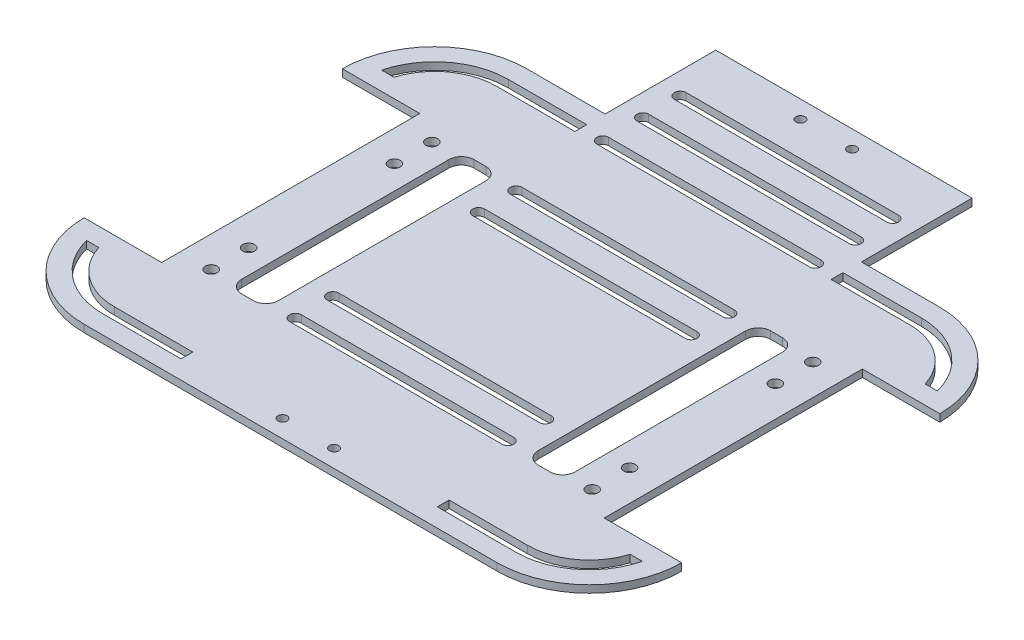
SolidWorks part; units mm, degrees
ref_plane "Front Plane" through (0, 0, 0) normal (0, 0, 1) x (1, 0, 0)
ref_plane "Top Plane" through (0, 0, 0) normal (0, 1, 0) x (1, 0, 0)
ref_plane "Right Plane" through (0, 0, 0) normal (1, 0, 0) x (0, 0, -1)
sketch "Sketch1" plane through (0, 0, 0) normal (0, 1, 0) x (1, 0, 0)
  line L0 (0, 0) -> (0, -79.375)
  line L1 (7.1438, -66.675) -> (-7.1437, -66.675)
  line L2 (50.8, 22.225) -> (76.2, 22.225)
  line L3 (-63.5, -47.625) -> (-50.8, -47.625)
  line L4 (-50.8, -47.625) -> (-50.8, 22.225)
  line L5 (63.5, -47.625) -> (50.8, -47.625)
  line L6 (50.8, -47.625) -> (50.8, 22.225)
  line L7 (-50.8, 22.225) -> (-76.2, 22.225)
  line L8 (0, 0) -> (-27.2811, 0)
  circle A0 centre (0, 0) radius 79.375
  circle A1 centre (-7.1437, -66.675) radius 1.5875
  circle A2 centre (7.1438, -66.675) radius 1.5875
  circle A3 centre (7.1438, 66.675) radius 1.5875
  circle A4 centre (-7.1437, 66.675) radius 1.5875
  point P7 (0, -66.675)
  dimension "D1" = 7.1437
  dimension "D3" = 50.8
  dimension "D6" = 3.175
  dimension "D2" = 12.7
  dimension "D4" = 69.85
  dimension "D5" = 47.625
extrude "Boss-Extrude5" add sketch "Sketch1" along normal blind 1.5875 contours A2 A0 L5 L6 L2 L7 L4 L3 A1 A3 region at (0, 0, -2.0947)
fillet "Fillet2" radius 2.54 1 edges at (-63.5, 0.7937, 47.625)
fillet "Fillet3" radius 2.54 1 edges at (63.5, 0.7937, 47.625)
fillet "Fillet4" radius 5.08 2 edges at (-76.2, 0.7937, -22.225) (76.2, 0.7937, -22.225)
sketch "Sketch2" plane through (0, 1.5875, 0) normal (0, 1, 0) x (1, 0, 0)
  line L0 (0, 0) -> (0, 79.375)
  line L1 (0, 0) -> (-67.0566, 0)
  line L2 (0, 0) -> (-61.0886, 27.6545)
  line L3 (0, 0) -> (-43.6778, 50.8806)
  line L4 (0, 0) -> (-63.2664, 22.225)
  line L5 (-50.8, 22.225) -> (-69.0955, 22.225) construction
  line L6 (0, 0) -> (0, 2.6153)
  line L7 (0, 0) -> (-39.0771, 54.4938)
  line L8 (0, 0) -> (-12.3858, 65.9028)
  line L9 (-62.5348, 28.3092) -> (-59.6424, 26.9998)
  line L10 (-43.6778, 50.8806) -> (-44.7118, 52.0852)
  line L11 (-43.6778, 50.8806) -> (-42.6438, 49.6761)
  line L12 (-39.0771, 54.4938) -> (-40.0022, 55.7839)
  line L13 (-39.0771, 54.4938) -> (-38.152, 53.2037)
  line L14 (-43.6778, 50.8806) -> (-42.6438, 49.6761)
  line L15 (-12.3858, 65.9028) -> (-12.0926, 64.3426)
  line L16 (-12.3858, 65.9028) -> (-12.679, 67.463)
  line L17 (61.5813, 22.225) -> (64.9466, 22.225)
  line L18 (50.8, 22.225) -> (69.0955, 22.225) construction
  line L19 (12.3858, 65.9028) -> (12.679, 67.463)
  line L20 (12.3858, 65.9028) -> (12.0926, 64.3426)
  line L21 (39.0771, 54.4938) -> (38.152, 53.2037)
  line L22 (43.6778, 50.8806) -> (42.6438, 49.6761)
  line L23 (39.0771, 54.4938) -> (40.0022, 55.7839)
  line L24 (43.6778, 50.8806) -> (42.6438, 49.6761)
  line L25 (43.6778, 50.8806) -> (44.7118, 52.0852)
  line L26 (62.5348, 28.3092) -> (59.6424, 26.9998)
  line L27 (-50.8, -41.2985) -> (-50.8, -43.7716)
  line L28 (-50.8, -47.625) -> (-50.8, 22.225) construction
  line L29 (50.8, -41.2985) -> (50.8, -46.1668)
  line L30 (50.8, -47.625) -> (50.8, 22.225) construction
  line L31 (39.0771, -54.4938) -> (40.0022, -55.7839)
  line L32 (39.0771, -54.4938) -> (38.152, -53.2037)
  line L33 (12.3858, -65.9028) -> (12.0926, -64.3426)
  line L34 (12.3858, -65.9028) -> (12.679, -67.463)
  line L35 (-12.3858, -65.9028) -> (-12.679, -67.463)
  line L36 (-12.3858, -65.9028) -> (-12.0926, -64.3426)
  line L37 (-39.0771, -54.4938) -> (-38.152, -53.2037)
  line L38 (-39.0771, -54.4938) -> (-40.0022, -55.7839)
  arc A0 (-63.2664, 22.225) -> (-50.8, -43.7716) centre (0, 0) ccw
  arc A1 (73.8199, 29.172) -> (-73.8199, 29.172) centre (0, 0) ccw construction
  circle A2 centre (-7.1437, 66.675) radius 2.3813
  circle A3 centre (7.1437, 66.675) radius 2.3813
  circle A4 centre (7.1437, -66.675) radius 2.3813
  circle A5 centre (-7.1437, -66.675) radius 2.3813
  arc A6 (12.679, -67.463) -> (40.0022, -55.7839) centre (0, 0) ccw
  arc A7 (-61.7686, 21.6988) -> (-50.8, -41.2985) centre (0, 0) ccw
  arc A8 (-44.7118, 52.0852) -> (-62.5348, 28.3092) centre (0, 0) ccw
  arc A9 (-42.6438, 49.6761) -> (-59.6424, 26.9998) centre (0, 0) ccw
  arc A10 (12.0926, 64.3426) -> (38.152, 53.2037) centre (0, 0) cw
  arc A11 (12.679, 67.463) -> (40.0022, 55.7839) centre (0, 0) cw
  arc A12 (42.6438, 49.6761) -> (59.6424, 26.9998) centre (0, 0) cw
  arc A13 (-12.679, 67.463) -> (-40.0022, 55.7839) centre (0, 0) ccw
  arc A14 (44.7118, 52.0852) -> (62.5348, 28.3092) centre (0, 0) cw
  arc A15 (-12.0926, 64.3426) -> (-38.152, 53.2037) centre (0, 0) ccw
  arc A16 (12.0926, -64.3426) -> (38.152, -53.2037) centre (0, 0) ccw
  arc A17 (-12.0926, -64.3426) -> (-38.152, -53.2037) centre (0, 0) cw
  arc A18 (50.8, -46.1668) -> (64.9466, 22.225) centre (0, 0) ccw
  arc A19 (50.8, -43.7716) -> (63.2664, 22.225) centre (0, 0) ccw
  arc A20 (50.8, -41.2985) -> (61.5813, 22.225) centre (0, 0) ccw
  arc A21 (-12.679, -67.463) -> (-40.0022, -55.7839) centre (0, 0) cw
  circle M13 centre (-7.1437, -66.675) radius 1.5875
  circle M14 centre (7.1438, -66.675) radius 1.5875
  circle M15 centre (7.1438, 66.675) radius 1.5875
  circle M16 centre (-7.1437, 66.675) radius 1.5875
  dimension "D2" = 4.7625
  dimension "D7" = 1.5875
  dimension "D8" = 3.175
  dimension "D1" = 5
  dimension "D3" = 25
  dimension "D4" = 5
  dimension "D5" = 25
extrude "Cut-Extrude1" cut sketch "Sketch2" against normal blind 2.54 contours A9 L3 L10 A8 L9 L2 | A15 L8 L16 A13 L12 L7 | A2 M16 | A3 M15 | A11 L19 L20 A10 L21 L23 | A14 L25 L22 A12 L26 | A21 L35 L36 A17 L37 L38 | A5 M13 | A4 M14 | A16 L33 L34 A6 L31 L32 region at (-53.2404, 1.5875, -39.9101) region at (-26.1525, 1.5875, -61.1833) region at (26.1525, 1.5875, -61.1833) region at (53.2404, 1.5875, -39.9101) region at (26.1525, 1.5875, 61.1833) region at (-26.1525, 1.5875, 61.1833) region at (-9.4576, 1.5875, -66.675) region at (4.8299, 1.5875, -66.675) region at (4.8299, 1.5875, 66.675) region at (-9.4576, 1.5875, 66.675)
sketch "Sketch3" plane through (0, 1.5875, 0) normal (0, 1, 0) x (1, 0, 0)
  line L0 (-50.8, 22.225) -> (-50.8, -47.625)
  line L1 (-50.8, -47.625) -> (-44.45, -47.625)
  line L2 (-50.8, 22.225) -> (-44.45, 22.225)
  line L3 (0, 0) -> (0, 32.9013)
  circle A0 centre (-44.45, -47.625) radius 1.5875
  circle A1 centre (-44.45, 22.225) radius 1.5875
  circle A2 centre (44.45, 22.225) radius 1.5875
  circle A3 centre (44.45, -47.625) radius 1.5875
  dimension "D2" = 3.175
  dimension "D4" = 3.175
  dimension "D1" = 6.35
  dimension "D3" = 6.35
extrude "Cut-Extrude2" cut sketch "Sketch3" against normal blind 2.54 contours A1 | A2 | A0 | A3 region at (-44.45, 1.5875, 46.0824) region at (-44.45, 1.5875, -23.7676) region at (44.45, 1.5875, -22.225) region at (44.45, 1.5875, 47.625)
sketch "Sketch4" plane through (0, 1.5875, 0) normal (0, 1, 0) x (1, 0, 0)
  line L0 (-44.45, -47.625) -> (-44.45, 22.225)
  line L1 (-44.45, 22.225) -> (-50.8, 22.225)
  line L2 (-50.8, -47.625) -> (-50.8, 22.225) construction
  line L3 (0, 0) -> (0, -67.5878)
  line L4 (44.45, -47.625) -> (44.45, 22.225)
  circle A0 centre (-44.45, 22.225) radius 1.5875
  circle A1 centre (-44.45, -12.7) radius 1.5875
  circle A2 centre (44.45, -12.7) radius 1.5875
  dimension "D2" = 3.175
  dimension "D1" = 69.85
extrude "Cut-Extrude3" cut sketch "Sketch4" against normal blind 2.54 contours L0 A1 | L0 A1 | A2 L4 | A2 L4 region at (-45.1238, 1.5875, 12.7) region at (-43.7762, 1.5875, 12.7) region at (43.7762, 1.5875, 12.7) region at (45.1238, 1.5875, 12.7)
sketch "Sketch5" plane through (0, 1.5875, 0) normal (0, 1, 0) x (1, 0, 0)
  line L0 (-50.8, -12.7) -> (-34.8, -12.7)
  line L1 (-50.8, -47.625) -> (-50.8, 22.225) construction
  line L2 (-50.8, 22.225) -> (-34.8, 22.225)
  line L3 (-34.8, 22.225) -> (-34.8, -12.7)
  line L4 (0, 0) -> (0, 64.5379)
  line L5 (-34.8, 22.225) -> (-19.8, 22.225)
  line L6 (-19.8, 22.225) -> (-19.8, -12.7)
  line L7 (-19.8, -12.7) -> (-34.8, -12.7)
  line L8 (19.8, -12.7) -> (34.8, -12.7)
  line L9 (19.8, 22.225) -> (19.8, -12.7)
  line L10 (34.8, 22.225) -> (19.8, 22.225)
  line L11 (34.8, 22.225) -> (34.8, -12.7)
  dimension "D1" = 16
  dimension "D2" = 16
extrude "Cut-Extrude4" cut sketch "Sketch5" against normal through all contours L7 L6 L5 L3 | L11 L10 L9 L8 region at (-27.3, 1.5875, -4.7625) region at (27.3, 1.5875, -4.7625)
fillet "Fillet5" radius 7.62 4 edges at (-19.8, 0.7937, 12.7) (-34.8, 0.7937, 12.7) (-19.8, 0.7937, -22.225) (-34.8, 0.7937, -22.225)
fillet "Fillet6" radius 7.62 4 edges at (34.8, 0.7937, 12.7) (34.8, 0.7937, -22.225) (19.8, 0.7937, -22.225) (19.8, 0.7937, 12.7)
sketch "Sketch6" plane through (0, 0, 0) normal (0, -1, 0) x (-1, 0, 0)
  circle A0 centre (0, 0) radius 79.375
extrude "Cut-Extrude5" cut sketch "Sketch6" against normal blind 0.5875
sketch "Sketch8" plane through (0, 1.5875, 0) normal (0, 1, 0) x (1, 0, 0)
  line L0 (-50.8, 22.225) -> (-50.8, 24.225)
  line L1 (-50.8, 24.225) -> (-80.2365, 24.225)
  line L2 (0, 0) -> (0, 19.3161)
  line L3 (0, 0) -> (-9.6505, 0)
  line L4 (50.8, 24.225) -> (80.2365, 24.225)
  line L5 (50.8, 22.225) -> (50.8, 24.225)
  line L6 (-50.8, -47.625) -> (-50.8, -49.625)
  line L7 (-50.8, -49.625) -> (-75.4506, -49.625)
  line L8 (50.8, -49.625) -> (75.4506, -49.625)
  line L9 (50.8, -47.625) -> (50.8, -49.625)
  line L10 (-50.8, -47.625) -> (-75.4506, -47.625)
  line L11 (-75.4506, -47.625) -> (-75.4506, -49.625)
  line L12 (50.8, -47.625) -> (75.4506, -47.625)
  line L13 (75.4506, -49.625) -> (75.4506, -47.625)
  line L14 (50.8, 22.225) -> (80.2365, 22.225)
  line L15 (80.2365, 22.225) -> (80.2365, 24.225)
  line L16 (-50.8, 22.225) -> (-80.2365, 22.225)
  line L17 (-80.2365, 22.225) -> (-80.2365, 24.225)
extrude "Cut-Extrude6" cut sketch "Sketch8" against normal blind 2.54 contours L10 L11 L7 L6 | L8 L13 L12 L9 | L14 L15 L4 L5 | L1 L17 L16 L0 region at (65.5183, 1.5875, -23.225) region at (-63.1253, 1.5875, 48.625) region at (63.1253, 1.5875, 48.625)
fillet "Fillet7" radius 2.54 4 edges at (-60.6806, 1.0875, 49.625) (60.6806, 1.0875, 49.625) (73.1353, 1.0875, -24.225) (-73.1353, 1.0875, -24.225)
sketch "Sketch11" plane through (0, 1.5875, 0) normal (0, 1, 0) x (1, 0, 0)
  line L1 (-11.0583, 60.7829) -> (11.2037, 60.7829)
  line L2 (-11.0583, 60.7829) -> (-11.0583, 72.1091)
  line L3 (-11.0583, 72.1091) -> (11.2037, 72.1091)
  line L4 (11.2037, 60.7829) -> (11.2037, 72.1091)
  line L5 (-11.0583, -61.658) -> (11.2037, -61.658)
  line L6 (-11.0583, -61.658) -> (-11.0583, -72.2032)
  line L7 (-11.0583, -72.2032) -> (11.2037, -72.2032)
  line L8 (11.2037, -61.658) -> (11.2037, -72.2032)
extrude "Boss-Extrude7" add sketch "Sketch11" against normal up to surface (1 mm away) up to face at (0, 0.5875, 5.2491)
sketch "Sketch12" plane through (0, 1.5875, 0) normal (0, 1, 0) x (1, 0, 0)
  line L0 (0, 0) -> (0, 79.375)
  line L1 (0, 0) -> (-6.75, 0)
  line L4 (0, 65.9028) -> (-6.75, 65.9028)
  line L5 (0, -65.9028) -> (-6.75, -65.9028)
  line L6 (-12.3858, -65.9028) -> (12.3858, -65.9028)
  line L7 (-12.0926, -64.3426) -> (-12.679, -67.463) construction
  line L8 (12.679, -67.463) -> (12.0926, -64.3426) construction
  arc A0 (73.8199, 29.172) -> (-73.8199, 29.172) centre (0, 0) ccw construction
  circle A1 centre (-6.75, 65.9028) radius 1.25
  circle A2 centre (6.75, 65.9028) radius 1.25
  circle A3 centre (6.75, -65.9028) radius 1.25
  circle A4 centre (-6.75, -65.9028) radius 1.25
  dimension "D1" = 2.5
  dimension "D2" = 13.5
extrude "Cut-Extrude7" cut sketch "Sketch12" against normal blind 2.54 contours A4 L6 | A4 L6 | L6 A3 | L6 A3 | A1 | A2 region at (-6.75, 1.5875, 66.4333) region at (-6.75, 1.5875, 65.3723) region at (6.75, 1.5875, 65.3723) region at (6.75, 1.5875, 66.4333) region at (-7.9646, 1.5875, -65.9028) region at (6.75, 1.5875, -65.9028)
sketch "Sketch14" plane through (0, 1.5875, 0) normal (0, 1, 0) x (1, 0, 0)
  circle A0 centre (-44.45, -12.7) radius 1.5875
  circle A2 centre (44.45, -12.7) radius 1.5875
  dimension "D1" = 3.175
extrude "Boss-Extrude8" add sketch "Sketch14" against normal up to surface (1 mm away) up to face at (-6.75, 0.5875, 64.6528)
sketch "Sketch15" plane through (0, 1.5875, 0) normal (0, 1, 0) x (1, 0, 0)
  line L0 (-44.45, 22.225) -> (-44.45, -1.0583)
  line L1 (-44.45, -1.0583) -> (-44.45, -24.3417)
  line L2 (0, 0) -> (0, 10.0728)
  line L3 (44.45, -1.0583) -> (44.45, -24.3417)
  circle A0 centre (-44.45, -1.0583) radius 1.5875
  circle A1 centre (-44.45, -24.3417) radius 1.5875
  circle A2 centre (44.45, -24.3417) radius 1.5875
  circle A3 centre (44.45, -1.0583) radius 1.5875
  dimension "D1" = 23.2833
  dimension "D2" = 3.175
  dimension "D3" = 23.2833
extrude "Cut-Extrude8" cut sketch "Sketch15" against normal blind 2.54 contours L1 A0 L0 | L0 A0 L1 | A1 | A2 | A3 region at (-43.7762, 1.5875, 1.0583) region at (-43.3592, 1.5875, 23.2509) region at (-45.1238, 1.5875, 1.0583) region at (45.5408, 1.5875, 23.2509) region at (43.3592, 1.5875, -0.0324)
sketch "Sketch16" plane through (0, 1.5875, 0) normal (0, 1, 0) x (1, 0, 0)
  line L0 (-44.45, -1.0583) -> (-51.5937, -1.0583)
  line L1 (-50.8, -49.625) -> (-56.413, -49.625) construction
  line L2 (-50.8, 24.225) -> (-51.5937, 24.225)
  line L3 (-50.8, 24.225) -> (-50.8, -49.625)
  line L4 (-50.8, -49.625) -> (-51.5937, -49.625)
  line L5 (-51.5937, 24.225) -> (-51.5937, -49.625)
  line L6 (0, 0) -> (0, 12.3631)
  line L7 (51.5937, 24.225) -> (51.5937, -49.625)
  line L8 (50.8, -49.625) -> (51.5937, -49.625)
  line L9 (50.8, 24.225) -> (50.8, -49.625)
  line L10 (50.8, 24.225) -> (51.5937, 24.225)
extrude "Boss-Extrude13" add sketch "Sketch16" against normal up to surface (1 mm away) contours L2 L5 L0 L3 | L0 L5 L4 L3 | L10 L9 L8 L7 region at (-51.1969, 1.5875, 25.3417) region at (-51.1969, 1.5875, -11.5833) region at (51.1969, 1.5875, 12.7) up to face at (44.45, 0.5875, 22.7542)
sketch "Sketch17" plane through (0, 1.5875, 0) normal (0, 1, 0) x (1, 0, 0)
  line L0 (0, 0) -> (0, 79.375)
  line L1 (0, 0) -> (-11.9199, 67.6013)
  line L2 (0, 0) -> (12.0176, 0)
  line L3 (0, 0) -> (-62.5348, 28.3092)
  line L4 (0, 0) -> (11.9199, 67.6013)
  line L5 (0, 0) -> (62.5348, 28.3092)
  line L6 (0, 0) -> (-40.0022, -55.7839)
  line L7 (0, 0) -> (11.9199, -67.6013)
  line L8 (0, 0) -> (-11.9199, -67.6013)
  line L9 (0, 0) -> (40.0022, -55.7839)
  arc A0 (73.8199, 29.172) -> (-73.8199, 29.172) centre (0, 0) ccw construction
  circle A1 centre (0, 0) radius 68.6441
  circle A2 centre (0, 0) radius 65.4691
  dimension "D1" = 10
extrude "Cut-Extrude10" cut sketch "Sketch17" against normal through all contours A2 L1 A1 L3 | A2 L5 A1 L4 | A2 L7 A1 L9 | A2 L6 A1 L8 region at (-40.5469, 1.5875, -52.2313) region at (12.2875, 1.5875, -65.9244) region at (-25.7975, 1.5875, 61.3039) region at (25.7975, 1.5875, 61.3039)
sketch "Sketch18" plane through (0, 1.5875, 0) normal (0, 1, 0) x (1, 0, 0)
  line L0 (0, 0) -> (0, 79.375)
  line L1 (0, 0) -> (-26.9517, 0)
  line L2 (0, 0) -> (-11.9199, 67.6013)
  line L3 (0, 0) -> (-34.3221, 59.4475)
  line L4 (0, 0) -> (-44.1236, 52.5844)
  line L5 (0, 0) -> (-59.4475, 34.3221)
  line L6 (-62.5348, 28.3092) -> (-59.6424, 26.9998)
  line L7 (0, 0) -> (11.9199, 67.6013)
  line L8 (0, 0) -> (34.3221, 59.4475)
  line L9 (0, 0) -> (44.1236, 52.5844)
  line L10 (0, 0) -> (59.4475, 34.3221)
  line L11 (0, 0) -> (44.1236, -52.5844)
  line L12 (0, 0) -> (-44.1236, -52.5844)
  line L13 (0, 0) -> (34.3221, -59.4475)
  line L14 (0, 0) -> (11.9199, -67.6013)
  line L15 (0, 0) -> (-11.9199, -67.6013)
  line L16 (0, 0) -> (-34.3221, -59.4475)
  line L17 (59.6424, 26.9998) -> (62.5348, 28.3092)
  line L18 (40.0022, -55.7839) -> (38.152, -53.2037)
  line L19 (-38.152, -53.2037) -> (-40.0022, -55.7839)
  arc A0 (73.8199, 29.172) -> (-73.8199, 29.172) centre (0, 0) ccw construction
  circle A1 centre (0, 0) radius 68.6441
  circle A2 centre (0, 0) radius 65.4691
  dimension "D1" = 20
  dimension "D2" = 10
  dimension "D3" = 20
extrude "Boss-Extrude16" add sketch "Sketch18" against normal up to surface (1 mm away) contours A2 L19 A1 L16 | A2 L13 A1 L18 | A2 L17 A1 L10 | A2 L9 A1 L8 | A2 L3 A1 L4 | A2 L5 A1 L6 region at (-38.4205, 1.5875, -54.8701) region at (-59.64, 1.5875, -30.6219) region at (38.4205, 1.5875, -54.8701) region at (59.64, 1.5875, -30.6219) region at (36.3389, 1.5875, 56.3393) region at (-36.3389, 1.5875, 56.3393) up to face at (25.6849, 0.5875, 61.0364)
sketch "Sketch19" plane through (0, 1.5875, 0) normal (0, 1, 0) x (1, 0, 0)
  line L0 (33.7, 150.1124) -> (33.7, 185.1124)
  line L1 (0, 79.375) -> (0, -79.375)
  line L2 (-51.5937, 24.225) -> (51.5937, 24.225)
  line L3 (-51.5937, 24.225) -> (-51.5937, -49.625)
  line L4 (-51.5937, -49.625) -> (51.5937, -49.625)
  line L5 (51.5937, 24.225) -> (51.5937, -49.625)
  line L6 (37.7, 90.1124) -> (149.7, 90.1124)
  line L7 (-172.4279, 149.4503) -> (-117.4279, 149.4503)
  line L8 (-172.4279, 149.4503) -> (-172.4279, 121.4503)
  line L9 (-172.4279, 121.4503) -> (-117.4279, 121.4503)
  line L10 (-117.4279, 149.4503) -> (-117.4279, 121.4503)
  line L11 (219.5866, 324.1917) -> (264.5866, 324.1917)
  line L12 (219.5866, 324.1917) -> (219.5866, 272.1917)
  line L13 (219.5866, 272.1917) -> (264.5866, 272.1917)
  line L14 (264.5866, 324.1917) -> (264.5866, 272.1917)
  line L15 (51.5937, -49.625) -> (11.5937, -49.625)
  line L16 (51.5937, -49.625) -> (51.5937, -14.625)
  line L17 (51.5937, -14.625) -> (11.5937, -14.625)
  line L18 (11.5937, -49.625) -> (11.5937, -14.625)
  line L19 (93.7, 90.1124) -> (93.7, 230.1124)
  line L21 (174.7, 115.1124) -> (153.7, 115.1124)
  line L22 (12.7, 185.1124) -> (33.7, 185.1124)
  line L23 (78.6997, 149.9601) -> (87.6997, 149.9296)
  line L24 (38.7, 167.1124) -> (38.7, 133.1124)
  line L25 (78.6427, 133.1124) -> (38.7, 133.1124)
  line L26 (78.7578, 167.1124) -> (78.6427, 133.1124)
  line L27 (78.7578, 167.1124) -> (38.7, 167.1124)
  line L28 (33.7, 150.1124) -> (12.7, 150.1124)
  line L29 (242.0866, 324.1917) -> (242.0866, 272.1917)
  line L30 (37.7, 210.1124) -> (58.953, 210.1124)
  line L31 (290.0855, 218.8978) -> (400.0855, 218.8978)
  line L32 (290.0855, 218.8978) -> (290.0855, 165.8978)
  line L33 (290.0855, 165.8978) -> (400.0855, 165.8978)
  line L34 (400.0855, 218.8978) -> (400.0855, 165.8978)
  line L35 (-58.953, -52.165) -> (-58.953, 24.225)
  line L36 (-51.5937, 24.225) -> (-71.5774, 24.225) construction
  line L37 (-58.953, 24.225) -> (-51.5937, 24.225)
  line L38 (-58.953, -52.165) -> (-51.5937, -49.625)
  line L39 (58.953, -52.165) -> (51.5937, -49.625)
  line L40 (58.953, 24.225) -> (51.5937, 24.225)
  line L41 (58.953, -52.165) -> (58.953, 24.225)
  line L42 (51.5937, 24.225) -> (51.5937, -49.625)
  line L43 (12.7, 120.1124) -> (12.7, 180.1124)
  line L44 (12.7, 180.1124) -> (22.7, 180.1124)
  line L45 (22.7, 180.1124) -> (22.7, 120.1124)
  line L46 (22.7, 120.1124) -> (12.7, 120.1124)
  line L47 (38.7, 150.1124) -> (33.7, 150.1124)
  line L49 (128.447, 230.1124) -> (128.447, 210.1124)
  line L50 (153.7, 150.1124) -> (153.7, 115.1124)
  line L51 (148.7, 150.1124) -> (153.7, 150.1124)
  line L52 (164.7, 120.1124) -> (174.7, 120.1124)
  line L53 (164.7, 180.1124) -> (164.7, 120.1124)
  line L54 (174.7, 180.1124) -> (164.7, 180.1124)
  line L55 (174.7, 120.1124) -> (174.7, 180.1124)
  line L56 (149.7, 210.1124) -> (128.447, 210.1124)
  line L57 (33.7, 150.1124) -> (33.7, 115.1124)
  line L58 (153.7, 150.1124) -> (174.7, 150.1124)
  line L59 (108.6422, 167.1124) -> (148.7, 167.1124)
  line L60 (108.6422, 167.1124) -> (108.7573, 133.1124)
  line L61 (108.7573, 133.1124) -> (148.7, 133.1124)
  line L62 (58.953, 230.1124) -> (58.953, 210.1124)
  line L63 (174.7, 185.1124) -> (153.7, 185.1124)
  line L64 (148.7, 167.1124) -> (148.7, 133.1124)
  line L65 (108.7003, 149.9601) -> (99.7003, 149.9296)
  line L66 (153.7, 150.1124) -> (153.7, 185.1124)
  line L67 (-325.826, 349.5435) -> (-272.826, 349.5435)
  line L68 (-325.826, 349.5435) -> (-325.826, 239.5435)
  line L69 (-325.826, 239.5435) -> (-272.826, 239.5435)
  line L70 (-272.826, 349.5435) -> (-272.826, 239.5435)
  line L71 (-215.9733, 300.1641) -> (-187.9733, 300.1641)
  line L72 (-215.9733, 300.1641) -> (-215.9733, 245.1641)
  line L73 (-215.9733, 245.1641) -> (-187.9733, 245.1641)
  line L74 (-187.9733, 300.1641) -> (-187.9733, 245.1641)
  line L75 (12.7, 115.1124) -> (33.7, 115.1124)
  line L76 (153.7, 180.1124) -> (153.7, 150.1124)
  line L78 (58.953, 230.1124) -> (58.953, 240.1124)
  line L79 (58.953, 240.1124) -> (128.447, 240.1124)
  line L80 (128.447, 230.1124) -> (128.447, 240.1124)
  arc A0 (73.8199, 29.172) -> (-73.8199, 29.172) centre (0, 0) ccw construction
  arc A1 (-58.2779, -53.8895) -> (58.2779, -53.8895) centre (0, 0) ccw construction
  arc A2 (-56.413, -49.625) -> (-58.2779, -53.8895) centre (-56.413, -52.165) ccw construction
  circle A3 centre (100.706, 94.8953) radius 1.25
  circle A4 centre (86.694, 235.3295) radius 1.25
  circle A5 centre (86.694, 94.8953) radius 1.25
  circle A6 centre (100.706, 235.3295) radius 1.25
  arc A7 (12.7, 115.1124) -> (37.7, 90.1124) centre (37.7, 115.1124) ccw
  arc A8 (174.7, 115.1124) -> (149.7, 90.1124) centre (149.7, 115.1124) cw
  arc A9 (12.7, 185.1124) -> (37.7, 210.1124) centre (37.7, 185.1124) cw
  arc A10 (174.7, 185.1124) -> (149.7, 210.1124) centre (149.7, 185.1124) ccw
  dimension "D15" = 55
  dimension "D1" = 103.1875
  dimension "D3" = 158.75
  dimension "D4" = 28
  dimension "D5" = 55
  dimension "D6" = 150
  dimension "D7" = 162
  dimension "D8" = 40
  dimension "D9" = 35
  dimension "D11" = 110
  dimension "D12" = 110
  dimension "D13" = 53
  dimension "D16" = 28
  dimension "D17" = 53
  dimension "D18" = 45
  dimension "D19" = 52
  dimension "D20" = 29.75
extrude "Boss-Extrude20" add sketch "Sketch19" along normal blind 2 separate body contours L63 A10 L56 L49 L80 L79 L78 L62 L30 A9 L22 L0 L24 L27 L26 L25 L57 L75 A7 L6 A8 L21 L50 L64 L61 L60 L59 L66 A4 A3 A5 | L26 L27 L24 L25 | L64 L59 L60 L61 region at (58.7001, 1.5875, -150.1206) region at (128.6999, 1.5875, -150.1206) region at (35.9078, 1.5875, -167.6124)
sketch "Sketch20" plane through (0, 3.5875, 0) normal (0, 1, 0) x (1, 0, 0)
  line L0 (33.7, 185.1124) -> (33.7, 180.0324)
  line L1 (33.7, 115.1124) -> (33.7, 185.1124) construction
  line L2 (42.05, 180.0324) -> (33.7, 180.0324)
  line L3 (33.7, 180.0324) -> (33.7, 175.0324)
  line L4 (33.7, 150.1124) -> (44.1466, 150.1124)
  line L5 (93.7, 240.1124) -> (93.7, 224.3413)
  line L6 (58.953, 240.1124) -> (128.447, 240.1124) construction
  circle A0 centre (42.05, 180.0324) radius 1.5875
  circle A1 centre (42.05, 169.8724) radius 1.5875
  circle A2 centre (42.05, 130.3524) radius 1.5875
  circle A3 centre (42.05, 120.1924) radius 1.5875
  circle A4 centre (145.35, 120.1924) radius 1.5875
  circle A5 centre (145.35, 130.3524) radius 1.5875
  circle A6 centre (145.35, 169.8724) radius 1.5875
  circle A7 centre (145.35, 180.0324) radius 1.5875
  dimension "D3" = 3.175
  dimension "D5" = 3.175
  dimension "D1" = 5.08
  dimension "D2" = 5
  dimension "D4" = 10.16
  dimension "D6" = 8.35
extrude "Cut-Extrude13" cut sketch "Sketch20" against normal blind 2 contours A0 | A1 | A2 | A3 | A4 | A5 | A6 | A7 region at (42.05, 3.5875, -178.4898) region at (42.05, 3.5875, -169.8724) region at (42.05, 3.5875, -130.3524) region at (42.05, 3.5875, -120.1924) region at (145.35, 3.5875, -120.1924) region at (145.35, 3.5875, -130.3524) region at (145.35, 3.5875, -169.8724) region at (145.35, 3.5875, -180.0324)
sketch "Sketch23" plane through (0, 3.5875, 0) normal (0, 1, 0) x (1, 0, 0)
  line L0 (64.903, 181.6324) -> (122.497, 181.6324)
  line L1 (122.497, 178.4324) -> (64.903, 178.4324)
  line L2 (37.7, 205.1124) -> (58.953, 205.1124)
  line L3 (122.497, 226.1324) -> (64.903, 226.1324)
  line L4 (37.7, 201.9124) -> (58.953, 201.9124)
  line L5 (122.497, 222.9324) -> (64.903, 222.9324)
  line L6 (122.497, 171.4724) -> (64.903, 171.4724)
  line L7 (64.903, 168.2724) -> (122.497, 168.2724)
  line L8 (169.0649, 190.1124) -> (165.7387, 190.1124)
  line L9 (93.7, 230.3124) -> (93.7, 236.6657)
  line L10 (58.953, 205.1124) -> (58.953, 201.9124)
  line L11 (-100.9547, 278.8038) -> (-40.9547, 278.8038)
  line L12 (-100.9547, 278.8038) -> (-100.9547, 248.8038)
  line L13 (-100.9547, 248.8038) -> (-40.9547, 248.8038)
  line L14 (-40.9547, 278.8038) -> (-40.9547, 248.8038)
  line L15 (122.497, 215.9724) -> (64.903, 215.9724)
  line L16 (-24.4507, 290.9638) -> (-63.4507, 290.9638)
  line L17 (-24.4507, 287.7638) -> (-63.4507, 287.7638)
  line L18 (-63.4507, 246.4638) -> (-24.4507, 246.4638)
  line L19 (-63.4507, 244.8638) -> (-24.4507, 244.8638)
  line L20 (-65.0507, 289.3638) -> (-65.0507, 244.8638)
  line L21 (-24.4507, 243.2638) -> (-63.4507, 243.2638)
  line L22 (-22.8507, 244.8638) -> (-22.8507, 289.3638)
  line L23 (122.497, 212.7724) -> (64.903, 212.7724)
  line L24 (18.3351, 190.1124) -> (21.6613, 190.1124)
  line L25 (12.7, 185.1124) -> (33.7, 185.1124) construction
  line L26 (64.903, 131.9524) -> (122.497, 131.9524)
  line L27 (122.497, 128.7524) -> (64.903, 128.7524)
  line L28 (122.497, 121.7924) -> (64.903, 121.7924)
  line L29 (64.903, 118.5924) -> (122.497, 118.5924)
  line L30 (128.447, 205.1124) -> (128.447, 201.9124)
  line L33 (64.903, 205.1124) -> (122.497, 205.1124)
  line L34 (64.903, 201.9124) -> (122.497, 201.9124)
  line L35 (128.447, 205.1124) -> (149.7, 205.1124)
  line L36 (128.447, 201.9124) -> (149.7, 201.9124)
  line L37 (33.7, 150.1124) -> (40.3143, 150.1124)
  line L38 (33.7, 115.1124) -> (33.7, 185.1124) construction
  line L39 (18.3351, 110.1124) -> (21.6613, 110.1124)
  line L40 (58.953, 95.1124) -> (58.953, 98.3124)
  line L41 (37.7, 98.3124) -> (58.953, 98.3124)
  line L42 (37.7, 95.1124) -> (58.953, 95.1124)
  line L43 (149.7, 95.1124) -> (128.447, 95.1124)
  line L44 (149.7, 98.3124) -> (128.447, 98.3124)
  line L45 (128.447, 95.1124) -> (128.447, 98.3124)
  line L46 (169.0649, 110.1124) -> (165.7387, 110.1124)
  line L47 (51.8765, 181.6324) -> (55.0765, 181.6324)
  line L48 (-34.8, 14.605) -> (-19.8, 14.605)
  line L49 (-34.8, 14.605) -> (-34.8, -5.08)
  line L50 (-34.8, -5.08) -> (-19.8, -5.08)
  line L51 (-19.8, 14.605) -> (-19.8, -5.08)
  line L52 (58.4765, 178.2324) -> (58.4765, 121.9924)
  line L53 (53.4765, 181.6324) -> (53.4765, 210.1124)
  line L54 (58.4765, 121.9924) -> (58.8603, 122.0299)
  line L55 (37.7, 210.1124) -> (58.953, 210.1124) construction
  line L56 (58.953, 210.1124) -> (58.953, 240.1124) construction
  line L57 (55.0765, 118.5924) -> (51.8765, 118.5924)
  line L58 (51.8765, 118.5924) -> (51.3797, 118.9575)
  line L59 (48.4765, 121.9924) -> (48.4765, 178.2324)
  line L60 (138.9235, 121.9924) -> (138.9235, 178.2324)
  line L61 (135.5235, 118.5924) -> (136.0203, 118.9575)
  line L62 (132.3235, 118.5924) -> (135.5235, 118.5924)
  line L63 (128.9235, 121.9924) -> (128.5397, 122.0299)
  line L64 (128.9235, 178.2324) -> (128.9235, 121.9924)
  line L65 (135.5235, 181.6324) -> (132.3235, 181.6324)
  arc A0 (-63.4507, 290.9638) -> (-63.4507, 287.7638) centre (-63.4507, 289.3638) ccw
  arc A1 (64.903, 226.1324) -> (64.903, 222.9324) centre (64.903, 224.5324) ccw
  arc A2 (122.497, 226.1324) -> (122.497, 222.9324) centre (122.497, 224.5324) cw
  arc A3 (64.903, 181.6324) -> (64.903, 178.4324) centre (64.903, 180.0324) ccw
  arc A4 (122.497, 181.6324) -> (122.497, 178.4324) centre (122.497, 180.0324) cw
  arc A5 (-24.4507, 290.9638) -> (-24.4507, 287.7638) centre (-24.4507, 289.3638) cw
  arc A6 (-63.4507, 246.4638) -> (-63.4507, 243.2638) centre (-63.4507, 244.8638) ccw
  arc A7 (-24.4507, 243.2638) -> (-24.4507, 246.4638) centre (-24.4507, 244.8638) ccw
  arc A8 (12.7, 185.1124) -> (37.7, 210.1124) centre (37.7, 185.1124) cw
  arc A9 (37.7, 205.1124) -> (18.3351, 190.1124) centre (37.7, 185.1124) ccw
  arc A10 (37.7, 201.9124) -> (21.6613, 190.1124) centre (37.7, 185.1124) ccw
  arc A11 (122.497, 168.2724) -> (122.497, 171.4724) centre (122.497, 169.8724) ccw
  arc A12 (64.903, 168.2724) -> (64.903, 171.4724) centre (64.903, 169.8724) cw
  arc A13 (149.7, 201.9124) -> (165.7387, 190.1124) centre (149.7, 185.1124) cw
  arc A14 (149.7, 205.1124) -> (169.0649, 190.1124) centre (149.7, 185.1124) cw
  arc A15 (64.903, 215.9724) -> (64.903, 212.7724) centre (64.903, 214.3724) ccw
  arc A16 (122.497, 215.9724) -> (122.497, 212.7724) centre (122.497, 214.3724) cw
  arc A17 (64.903, 131.9524) -> (64.903, 128.7524) centre (64.903, 130.3524) ccw
  arc A18 (122.497, 131.9524) -> (122.497, 128.7524) centre (122.497, 130.3524) cw
  arc A19 (122.497, 118.5924) -> (122.497, 121.7924) centre (122.497, 120.1924) ccw
  arc A20 (64.903, 118.5924) -> (64.903, 121.7924) centre (64.903, 120.1924) cw
  arc A21 (37.7, 98.3124) -> (21.6613, 110.1124) centre (37.7, 115.1124) cw
  arc A22 (37.7, 95.1124) -> (18.3351, 110.1124) centre (37.7, 115.1124) cw
  arc A23 (149.7, 95.1124) -> (169.0649, 110.1124) centre (149.7, 115.1124) ccw
  arc A24 (149.7, 98.3124) -> (165.7387, 110.1124) centre (149.7, 115.1124) ccw
  arc A25 (51.8765, 181.6324) -> (48.4765, 178.2324) centre (51.8765, 178.2324) ccw
  arc A26 (55.0765, 118.5924) -> (58.4765, 121.9924) centre (55.0765, 121.9924) ccw
  arc A27 (55.0765, 181.6324) -> (58.4765, 178.2324) centre (55.0765, 178.2324) cw
  arc A28 (51.8765, 118.5924) -> (48.4765, 121.9924) centre (51.8765, 121.9924) cw
  arc A29 (135.5235, 118.5924) -> (138.9235, 121.9924) centre (135.5235, 121.9924) ccw
  arc A30 (132.3235, 181.6324) -> (128.9235, 178.2324) centre (132.3235, 178.2324) ccw
  arc A31 (132.3235, 118.5924) -> (128.9235, 121.9924) centre (132.3235, 121.9924) cw
  arc A32 (135.5235, 181.6324) -> (138.9235, 178.2324) centre (135.5235, 178.2324) cw
  arc A33 (64.903, 205.1124) -> (64.903, 201.9124) centre (64.903, 203.5124) ccw
  arc A34 (122.497, 201.9124) -> (122.497, 205.1124) centre (122.497, 203.5124) ccw
  point P0 (93.7, 205.1124)
  point P52 (93.7, 201.9124)
  dimension "D3" = 3.2
  dimension "D1" = 30
  dimension "D6" = 5
  dimension "D4" = 5
  dimension "D2" = 60
  dimension "D5" = 5
  dimension "D7" = 15
  dimension "D8" = 1.6
  dimension "D9" = 5.4765
extrude "Cut-Extrude18" cut sketch "Sketch23" against normal blind 2 contours A10 L4 L53 L2 A9 L24 | L53 L4 L10 L2 | L34 A34 L33 A33 | A16 L15 A15 L23 | A2 L3 A1 L5 | A14 L35 L30 L36 A13 L8 | A28 L57 A26 L52 A27 L47 A25 L59 | A12 L7 A11 L6 | A4 L0 A3 L1 | A32 L65 A30 L64 A31 L62 A29 L60 | A22 L42 L40 L41 A21 L39 | A24 L44 L45 L43 A23 L46 | A20 L29 A19 L28 | A18 L26 A17 L27 | L34 A34 L33 A33 region at (93.7, 3.5875, -180.0324) region at (53.4765, 3.5875, -150.1124) region at (45.5883, 3.5875, -204.7303) region at (56.2148, 3.5875, -203.5124) region at (93.7, 3.5875, -224.5324) region at (93.7, 3.5875, -169.8724) region at (167.4018, 3.5875, -190.5454) region at (93.7, 3.5875, -214.3724) region at (93.7, 3.5875, -130.3524) region at (93.7, 3.5875, -120.1924) region at (93.7, 3.5875, -203.5124) region at (19.9982, 3.5875, -109.6794) region at (139.0735, 3.5875, -95.5454) region at (133.9235, 3.5875, -150.1124)
sketch "Sketch24" plane through (0, 3.5875, 0) normal (0, 1, 0) x (1, 0, 0)
  circle A0 centre (0, 0) radius 79.375
extrude "Cut-Extrude20" cut sketch "Sketch24" against normal through all
